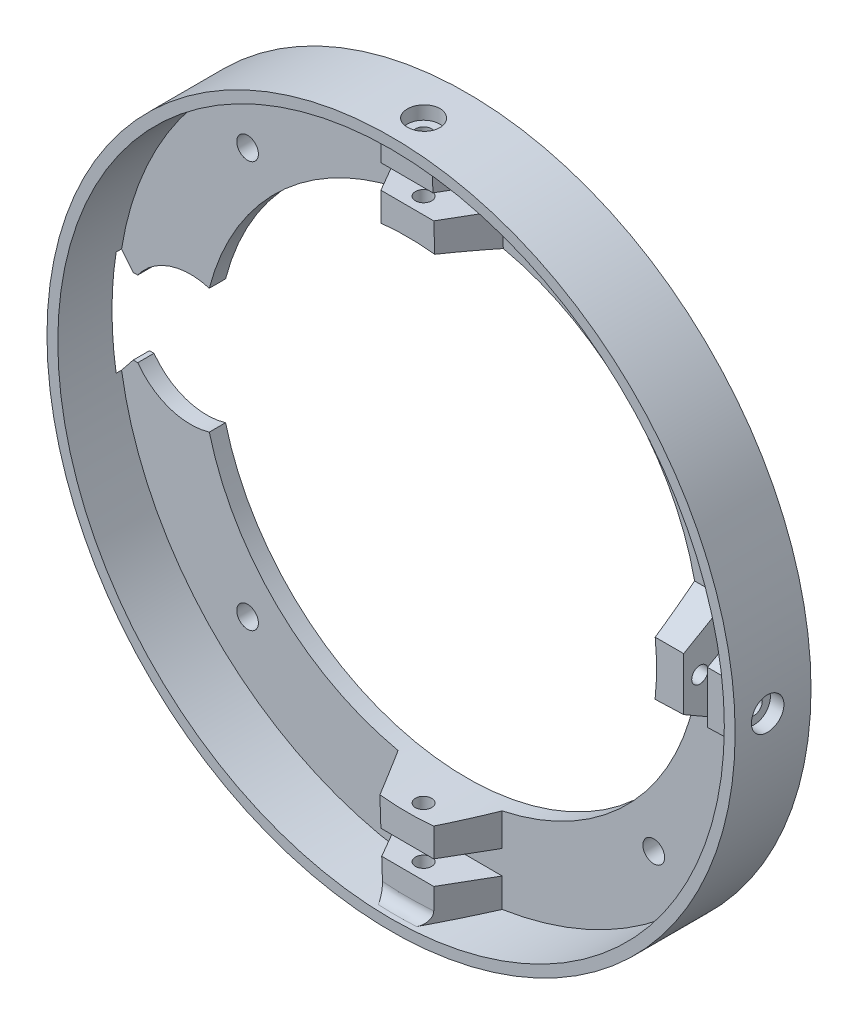
SolidWorks part; units mm, degrees
ref_plane "Front Plane" through (0, 0, 0) normal (0, 0, 1) x (1, 0, 0)
ref_plane "Top Plane" through (0, 0, 0) normal (0, 1, 0) x (1, 0, 0)
ref_plane "Right Plane" through (0, 0, 0) normal (1, 0, 0) x (0, 0, -1)
other "Graphic1"
other "Graphic (Closed) -1"
sketch "Sketch1" plane through (0, 0, 0) normal (0, 1, 0) x (1, 0, 0)
  line L0 (-61.5, -3) -> (-61.5, -14)
  line L1 (-46, 0) -> (-63.5, 0)
  line L3 (-61.5, -14) -> (-63.5, -14)
  line L4 (-63.5, 0) -> (-63.5, -14)
  line L5 (-63.5, 0) -> (-46, 0)
  line L6 (-63.5, 0) -> (-63.5, -3.5)
  line L7 (-61.5, -3) -> (-46, -3)
  line L8 (-46, 0) -> (-46, -3)
  line L9 (0, -0.5) -> (0, -27.4365) construction
  dimension "D1" = 46
  dimension "D2" = 14
  dimension "D3" = 3
  dimension "D4" = 63.5
  dimension "D5" = 2
revolve "Revolve1" add sketch "Sketch1" angle 360 about L9
sketch "Sketch2" plane through (0, 0, 0) normal (0, 0, -1) x (-1, 0, 0)
  line L1 (57.7468, 7) -> (73.2556, 7)
  line L2 (57.7468, -7) -> (73.2556, -7)
  line L3 (73.2556, 7) -> (73.2556, -7)
  arc A0 (57.7468, 7) -> (57.7468, -7) centre (48, 0) ccw
  dimension "D2" = 24
  dimension "D1" = 48
  dimension "D3" = 14
extrude "Cut-Extrude1" cut sketch "Sketch2" against normal blind 4
chamfer "Chamfer1" distance 5 angle 45 2 edges at (-63.113, -7, 2) (-63.113, 7, 2) first distance on face at (-31.5565, 0, 2)
sketch "Sketch3" plane through (0, 0, 3) normal (0, 0, 1) x (1, 0, 0)
  line L0 (-9.5023, -50.9595) -> (-9.7117, -44.9631)
  line L2 (0, 0) -> (0, -38.9343) construction
  line L3 (9.4977, -45.0088) -> (9.4977, -51.0088)
  line L4 (9.4977, -51.0088) -> (-9.5023, -50.9595)
  line L5 (9.4977, -55.4088) -> (-9.3486, -55.3599)
  line L6 (9.4977, -55.4088) -> (9.4977, -60.7622)
  line L7 (-9.3486, -55.3599) -> (-9.1581, -60.8143)
  arc A0 (-9.7117, -44.9631) -> (9.4977, -45.0088) centre (0, 0) ccw
  arc A1 (-44.5417, -11.4909) -> (-44.5417, 11.4909) centre (0, 0) ccw construction
  arc A2 (9.4977, -60.7622) -> (-9.1581, -60.8143) centre (0, 0) cw
  arc A3 (-60.7328, -9.6841) -> (-60.7328, 9.6841) centre (0, 0) ccw construction
  circle A4 centre (0, 0) radius 61.5 construction
  dimension "D3" = 6
  dimension "D2" = 0
  dimension "D1" = 2
  dimension "D4" = 6
  dimension "D5" = 19
  dimension "D6" = 4.4
extrude "Boss-Extrude1" add sketch "Sketch3" along normal blind 8
chamfer "Chamfer2" distance 8 angle 30 4 edges at (-9.2534, -58.0871, 11) (-9.607, -47.9613, 11) (9.4977, -48.0088, 11) (9.4977, -58.0855, 11) first distance on face at (-9.2534, -58.0871, 7) first distance on face at (-9.607, -47.9613, 7) first distance on face at (9.4977, -48.0088, 7) first distance on face at (9.4977, -58.0855, 7)
pattern_circular "CirPattern1" count 3 every 90 about axis through (0, 0, 0) along (0, 0, 1) of "Boss-Extrude1", "Chamfer2"
fillet "Fillet1" radius 2 3 edges at (61.4997, 0.1808, 11) (-0.1808, 61.4997, 11) (0.1808, -61.4997, 11)
sketch "Sketch4" plane through (0, 0, 0) normal (0, 0, -1) x (-1, 0, 0)
  line L0 (0, 0) -> (-37.4767, 37.4767) construction
  line L1 (0, 0) -> (-92.8805, 0) construction
  circle A0 centre (-37.4767, 37.4767) radius 2
  circle A1 centre (37.4767, 37.4767) radius 2
  circle A2 centre (37.4767, -37.4767) radius 2
  circle A3 centre (-37.4767, -37.4767) radius 2
  point P14 (0, 0)
  dimension "D3" = 4
  dimension "D1" = 45
  dimension "D2" = 53
  dimension "D4" = 4
extrude "Cut-Extrude2" cut sketch "Sketch4" against normal blind 10 contours A0
sketch "Sketch5" plane through (0, 0, 0) normal (0, 1, 0) x (1, 0, 0)
  line L0 (46, 0) -> (-44.5417, 0) construction
  circle A0 centre (0, -8) radius 1.5
  dimension "D1" = 3
  dimension "D2" = 8
extrude "Cut-Extrude3" cut sketch "Sketch5" against normal blind 158
ref_plane "Plane1" through (0, -65, 0) normal (0, 1, 0) x (1, 0, 0)
sketch "Sketch7" plane through (0, -65, 0) normal (0, 1, 0) x (1, 0, 0)
  circle A0 centre (0, -8) radius 3
  dimension "D1" = 6
extrude "Cut-Extrude5" cut sketch "Sketch7" along normal blind 4
pattern_circular "CirPattern3" count 3 every 90 about axis through (0, 0, 0) along (0, 0, 1) of "Cut-Extrude5", "Cut-Extrude3"
